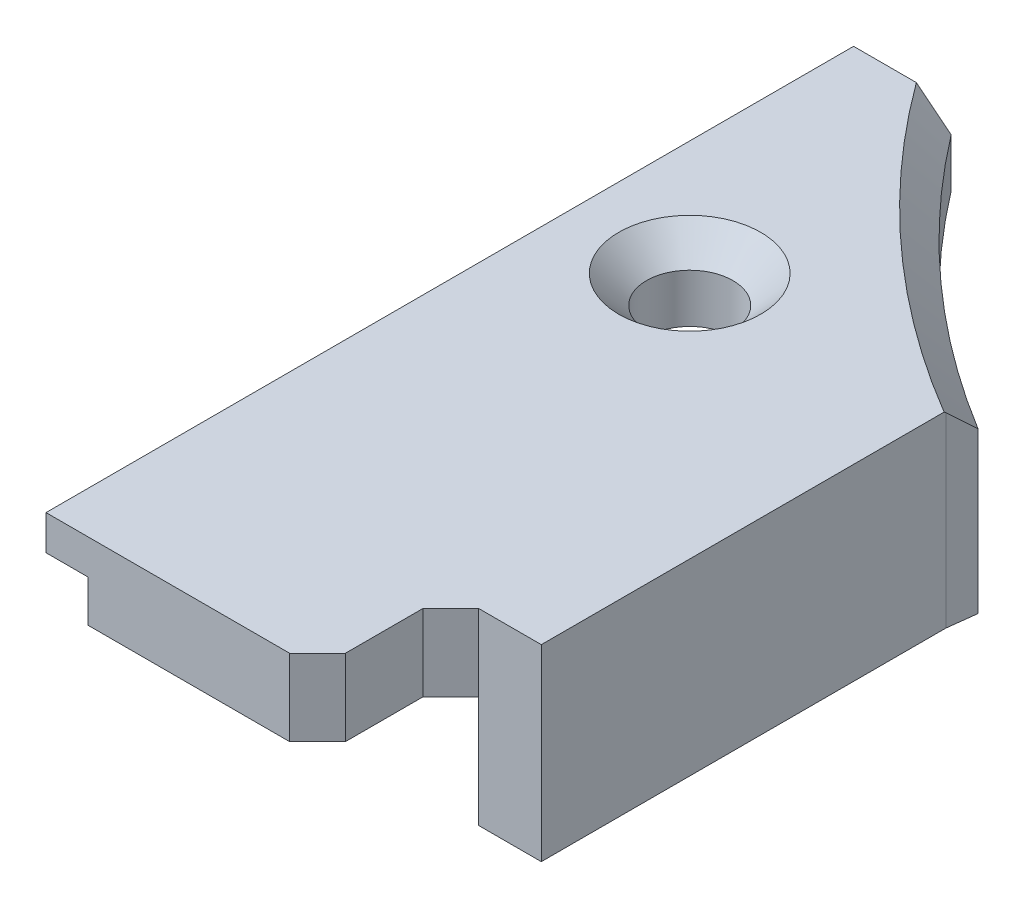
SolidWorks part; units mm, degrees
other "标注1"
sketch "草图7" plane through (25.8753, 2.75, 18.9999) normal (0.027, 0.4641, 0.8853) x (0.9619, 0.2291, -0.1494)
ref_plane "前视基准面" through (0, 0, 0) normal (0, 0, 1) x (1, 0, 0)
ref_plane "上视基准面" through (0, 0, 0) normal (0, 1, 0) x (1, 0, 0)
ref_plane "右视基准面" through (0, 0, 0) normal (1, 0, 0) x (0, 0, -1)
sketch "底座-前" plane through (0, 0, 0) normal (0, 1, 0) x (1, 0, 0)
  line L2 (-24.7152, 2.0807) -> (-24.5, 0.3125) construction
  line L6 (-22.5, -14.2499) -> (-22.5, -7.2636) construction
  line L7 (26.5, -14.2499) -> (22.5, -14.2499)
  line L8 (-22.5, -7.2636) -> (-24.5, -7.2636) construction
  line L9 (-24.5, -7.2636) -> (-24.5, 0.3125) construction
  line L10 (-24.5, 0.3125) -> (-25.1116, 5.3379) construction
  line L11 (22.5, -14.2499) -> (22.5, -7.2636)
  line L12 (-26.5, 1.2398) -> (-26.5, -14.2499) construction
  line L13 (-26.5, -14.2499) -> (-22.5, -14.2499) construction
  line L14 (22.5, -7.2636) -> (24.5, -7.2636)
  line L15 (26.5, 1.2398) -> (26.5, -14.2499)
  line L16 (-4.1009, 11.812) -> (-4.1009, 8.358) construction
  line L17 (-4.1009, 8.358) -> (4.1009, 8.358) construction
  line L18 (4.1009, 8.358) -> (4.1009, 11.8106) construction
  line L19 (-16.253, 10) -> (-4.1009, 10) construction
  line L20 (-4.1009, 10) -> (-4.1009, 8.358) construction
  line L21 (4.1009, 8.358) -> (4.1009, 10) construction
  line L22 (0, 0.0001) -> (0, -23.6618) construction
  line L23 (24.5, -7.2636) -> (24.5, 0.3125)
  line L24 (4.1009, 10) -> (12.5, 10) construction
  line L25 (12.5, 10) -> (12.5, -14.2499)
  line L26 (12.5, -14.2499) -> (-26.5, -14.2499) construction
  line L27 (24.7152, 2.0807) -> (24.5, 0.3125)
  line L28 (12.5, 10) -> (16.253, 10)
  line L29 (12.5, -14.2499) -> (22.5, -14.2499)
  arc A1 (-26.5, 2.4898) -> (-24.8662, 3.3216) centre (-28.6129, 8.6608) ccw construction
  arc A2 (26.5, 1.2398) -> (24.7152, 2.0807) centre (28.3556, 7.493) cw
  arc A3 (-25.1116, 5.3379) -> (-57.77, 17.2644) centre (-45.4537, 0.3125) ccw construction
  arc A4 (-26.5, 1.2398) -> (-24.7152, 2.0807) centre (-28.3556, 7.493) ccw construction
  arc A5 (-17.503, 10) -> (-24.8662, 3.3216) centre (-44.5319, 32.4021) cw construction
  arc A6 (-16.253, 10) -> (-24.7152, 2.0807) centre (-44.1427, 31.321) cw construction
  circle A7 centre (0, 6.108) radius 1.55 construction
  circle A8 centre (-16.866, 0) radius 1.55 construction
  arc A9 (16.253, 10) -> (24.7152, 2.0807) centre (44.1427, 31.321) ccw
  circle A10 centre (16.866, 0) radius 1.55
  dimension "D1" = 1.25
  dimension "D2" = 1.25
  dimension "D3" = 1.25
  dimension "D4" = 16.866
  dimension "D5" = 12.5
  dimension "D6" = 9.9999
  dimension "D7" = 14.25
  dimension "D8" = 22.5
  dimension "D9" = 26.5
  dimension "D10" = 24.5
  dimension "D11" = 7.2637
extrude "底座-1" add sketch "底座-前" along normal blind 2.75 contours A9 L28 L25 L29 L11 L14 L23 L27 region at (17.7884, 0, 3.1011)
sketch "底座-后" plane through (0, 0, 0) normal (0, 1, 0) x (1, 0, 0)
  line L0 (12.5, -14.2499) -> (12.5, -18.9999)
  line L1 (12.5, -18.9999) -> (22.5, -18.9999)
  line L2 (22.5, -18.9999) -> (22.5, -14.2499)
  line L3 (22.5, -14.2499) -> (12.5, -14.2499)
  dimension "D1" = 4.75
extrude "底座-2" add sketch "底座-后" along normal up to surface (2.75 mm away) up to face at (19.9549, 2.75, 2.6232)
sketch "底座卡榫" plane through (0, 0, 0) normal (0, 1, 0) x (1, 0, 0)
  line L1 (24.7152, 2.0807) -> (24.5, 0.3125)
  line L5 (0, 0) -> (0, 20.0235) construction
  line L6 (24.7152, 2.0807) -> (24.5, 0.3125) construction
  line L11 (22.5, -18.9999) -> (22.5, -7.2636) construction
  line L17 (22.5, -7.2636) -> (24.5, -7.2636) construction
  line L21 (25.75, 0.3125) -> (26.2135, 4.1214) construction
  line L22 (25.75, 0.3125) -> (24.5, 0.3125) construction
  line L24 (25.8753, 1.3423) -> (25.75, 0.3125)
  line L25 (22.5, -14.2136) -> (23.5, -14.2136)
  line L26 (22.5, -7.2636) -> (22.5, -14.2136)
  line L27 (23.5, -7.2636) -> (22.5, -7.2636)
  line L28 (24.5, -7.2636) -> (24.5, -14.2136)
  line L29 (24.5, -7.2636) -> (24.5, 0.3125)
  line L30 (25.75, -14.2136) -> (25.75, 0.3125)
  line L31 (24.5, -14.2136) -> (25.75, -14.2136)
  line L32 (23.5, -14.2136) -> (24.5, -14.2136)
  line L33 (23.5, -7.2636) -> (23.5, -14.2136)
  line L34 (24.5, -7.2636) -> (23.5, -7.2636)
  line L35 (24.5, -7.2636) -> (24.5, 0.3125) construction
  arc A2 (24.7152, 2.0807) -> (25.8753, 1.3423) centre (44.1427, 31.321) ccw
  arc A3 (16.253, 10) -> (24.7152, 2.0807) centre (44.1427, 31.321) ccw construction
  point P15 (25.125, -14.2136)
  dimension "D1" = 1.25
  dimension "D2" = 6.95
  dimension "D3" = 1
extrude "底座卡榫补齐" add sketch "底座卡榫" along normal up to surface (2.75 mm away) contours A2 L1 L29 L28 L31 L30 L24 | L28 L34 L33 L32 | L33 L27 L26 L25 region at (25.1278, 0, 6.2521) region at (24, 0, 10.7386) region at (23, 0, 10.7386) up to face at (19.9549, 2.75, 3.8107)
extrude "底座卡榫-注意PCB突出部分" add sketch "底座卡榫<6>" against normal blind 4 contours L28 L34 L33 L32 | A2 L1 L29 L28 L31 L30 L24 region at (25.1278, 0, 6.2521) region at (24, 0, 10.7386)
sketch "底座卡榫<6>" plane through (0, 0, 0) normal (0, 1, 0) x (1, 0, 0) same geometry as "底座卡榫"
sketch "草图4" plane through (0, 0, 0) normal (0, 1, 0) x (1, 0, 0)
  line L0 (12.5, 10) -> (14.25, 10)
  line L1 (12.5, 10) -> (16.253, 10) construction
  line L2 (14.25, 10) -> (14.25, -18.9999)
  line L3 (12.5, -18.9999) -> (22.5, -18.9999) construction
  line L4 (14.25, -18.9999) -> (12.5, -18.9999)
  line L5 (12.5, -18.9999) -> (12.5, 10)
  dimension "D1" = 1.75
extrude "卡榫切除" cut sketch "草图4" along normal blind 1.5
sketch "草图5" plane through (0, 0, 0) normal (0, 1, 0) x (1, 0, 0)
  line L0 (12.5, 10) -> (12.75, 10)
  line L1 (12.5, 10) -> (16.253, 10) construction
  line L2 (12.75, 10) -> (12.75, -18.9999)
  line L3 (12.5, -18.9999) -> (22.5, -18.9999) construction
  line L4 (12.75, -18.9999) -> (12.5, -18.9999)
  line L5 (12.5, -18.9999) -> (12.5, 10)
  dimension "D1" = 0.25
extrude "配合切除-2" cut sketch "草图5" along normal through all
chamfer "倒角1" distance 1 angle 45 3 edges at (22.5, 1.375, 18.9999) (20.6617, 2.75, -5.2238) (22.5, 1.375, 14.2136)
chamfer "倒角2" distance 1 angle 45 1 edges at (16.866, 2.75, 1.55)
sketch "草图6" plane through (0, -4, 0) normal (0, -1, 0) x (1, 0, 0)
  line L0 (24.7152, -2.0807) -> (24.5, -0.3125)
  line L1 (24.5, -0.3125) -> (24.5, 7.2636)
  line L2 (24.5, 7.2636) -> (23.5, 7.2636)
  line L3 (23.5, 7.2636) -> (23.5, 7.5136)
  line L4 (23.5, 7.2636) -> (23.5, 14.2136) construction
  line L5 (23.5, 7.5136) -> (24.75, 7.5136)
  line L6 (24.75, 7.5136) -> (24.75, -0.3125)
  line L7 (24.75, -0.3125) -> (24.9466, -1.9283)
  arc A0 (25.8753, -1.3423) -> (24.7152, -2.0807) centre (44.1427, -31.321) ccw construction
  arc A1 (24.7152, -2.0807) -> (24.9466, -1.9283) centre (44.1427, -31.321) cw
  dimension "D1" = 0.25
  dimension "D2" = 0.25
  dimension "D3" = 0.2482
extrude "切除-拉伸4" cut sketch "草图6" against normal up to surface (4 mm away) from surface up to face at (16.866, 0, 1.55) starting at face at (24.7609, -4, 4.864)
